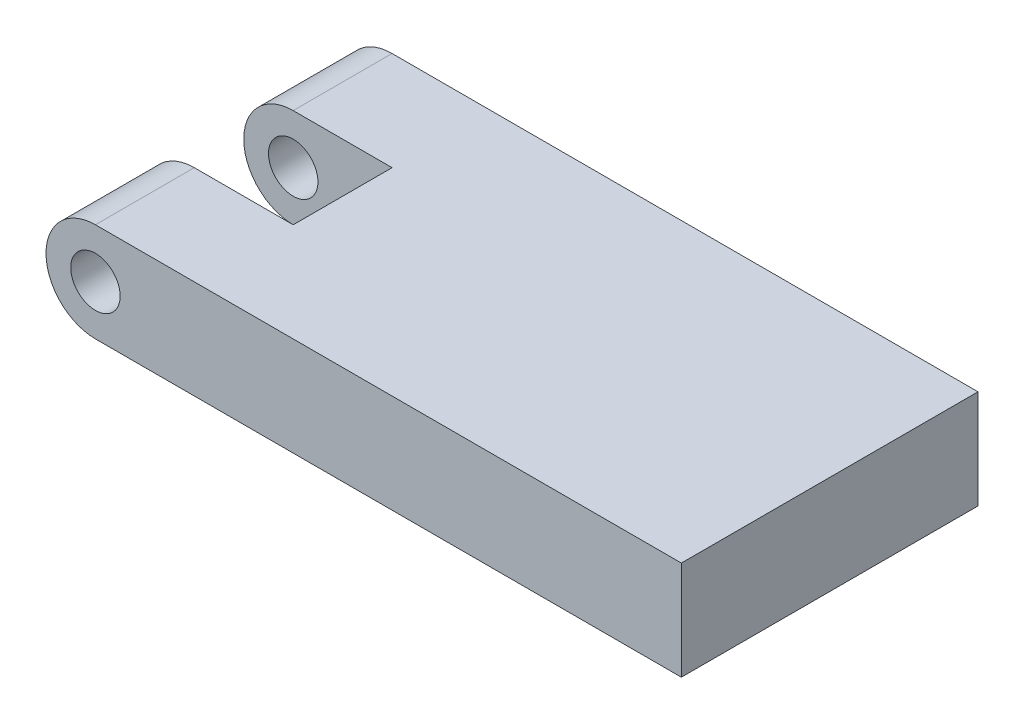
SolidWorks part; units mm, degrees
ref_plane "Front Plane" through (0, 0, 0) normal (0, 0, 1) x (1, 0, 0)
ref_plane "Top Plane" through (0, 0, 0) normal (0, 1, 0) x (1, 0, 0)
ref_plane "Right Plane" through (0, 0, 0) normal (1, 0, 0) x (0, 0, -1)
sketch "Sketch1" plane through (0, 0, 0) normal (0, 0, 1) x (1, 0, 0)
  line L0 (0, 10) -> (53.5123, 10)
  line L1 (53.5123, 10) -> (53.5123, -10)
  line L2 (53.5123, -10) -> (0, -10)
  circle A0 centre (0, 0) radius 10
  dimension "D1" = 20
extrude "Boss-Extrude1" add sketch "Sketch1" along normal blind 60 contours A0 | A0 L2 L1 L0 region at (30.6286, 0, 0) region at (0, 0, 0)
ref_plane "Plane1" through (0, 0, 0) normal (1, 0, 0) x (0, 0, -1)
sketch "Sketch2" plane through (0, 0, 0) normal (1, 0, 0) x (0, 0, -1)
  line L0 (0, 0) -> (-60, 0) construction
  line L1 (-60, 10) -> (-60, -10) construction
  line L3 (-20, 14.4724) -> (-40, 14.4724)
  line L4 (-20, 14.4724) -> (-20, -14.4724)
  line L5 (-20, -14.4724) -> (-40, -14.4724)
  line L6 (-40, 14.4724) -> (-40, -14.4724)
  line L7 (-20, 14.4724) -> (-40, -14.4724) construction
  line L8 (-20, -14.4724) -> (-40, 14.4724) construction
  point P5 (-30, 0)
  dimension "D1" = 20
extrude "Cut-Extrude1" cut sketch "Sketch2" against normal blind 40 and the other way blind 20
sketch "Sketch3" plane through (0, 0, 60) normal (0, 0, 1) x (1, 0, 0)
  circle A0 centre (0, 0) radius 5
  dimension "D1" = 10
extrude "Cut-Extrude3" cut sketch "Sketch3" against normal blind 120
ref_plane "Plane2" through (0, 0, 50) normal (0, 0, 1) x (1, 0, 0)
sketch "Sketch4" plane through (53.5123, 0, 0) normal (1, 0, 0) x (0, 0, -1)
  line L4 (0, -10) -> (0, 10)
  line L5 (0, 10) -> (-60, 10)
  line L6 (-60, 10) -> (-60, -10)
  line L7 (-60, -10) -> (0, -10)
  line L8 (0, -10) -> (0, 10)
  line L9 (0, 10) -> (-60, 10)
  line L10 (-60, 10) -> (-60, -10)
  line L11 (-60, -10) -> (0, -10)
  dimension "D1" = 0
extrude "Boss-Extrude2" add sketch "Sketch4" along normal blind 65
